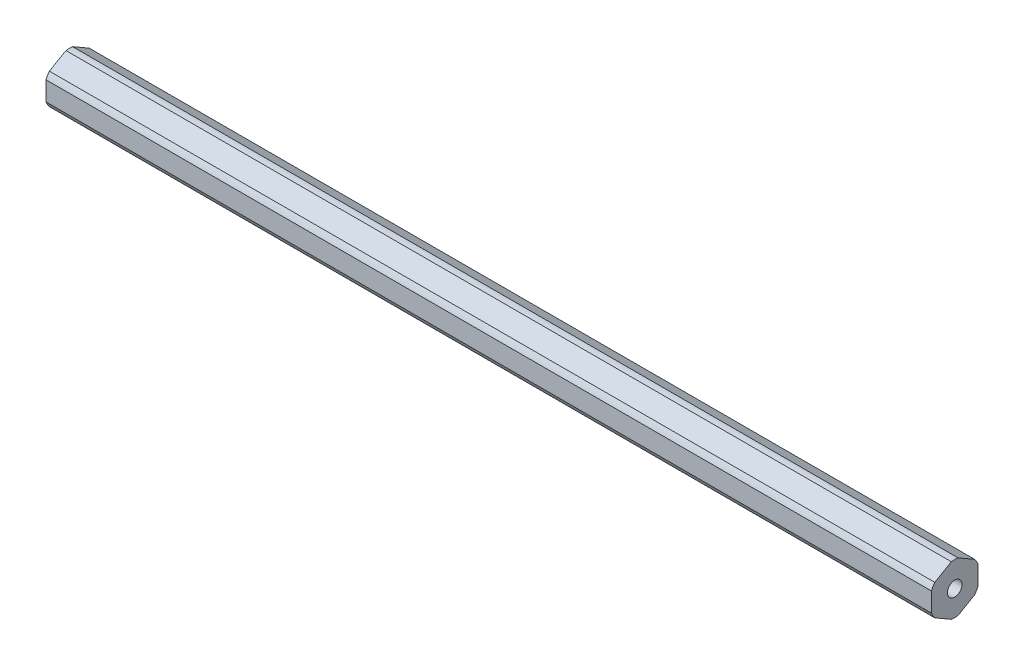
SolidWorks part; units mm, degrees
material "6061 Alloy"
ref_plane "Front Plane" through (0, 0, 0) normal (0, 0, 1) x (1, 0, 0)
ref_plane "Top Plane" through (0, 0, 0) normal (0, 1, 0) x (1, 0, 0)
ref_plane "Right Plane" through (0, 0, 0) normal (1, 0, 0) x (0, 0, -1)
ref_plane "Plane1" through (914.4, 0, 0) normal (1, 0, 0) x (0, 0, -1)
sketch "Sketch1" plane through (914.4, 0, 0) normal (1, 0, 0) x (0, 0, -1)
  line L0 (-5.4343, -4.1949) -> (-0.9157, -6.8037)
  line L1 (0.9157, -6.8037) -> (5.4343, -4.1949)
  line L2 (6.35, -2.6088) -> (6.35, 2.6088)
  line L3 (5.4343, 4.1949) -> (0.9157, 6.8037)
  line L4 (-0.9157, 6.8037) -> (-5.4343, 4.1949)
  line L5 (-6.35, 2.6088) -> (-6.35, -2.6088)
  circle A0 centre (0, 0) radius 1.9939
  arc A1 (-6.35, -2.6088) -> (-5.4343, -4.1949) centre (0, 0) ccw
  arc A2 (-0.9157, -6.8037) -> (0.9157, -6.8037) centre (0, 0) ccw
  arc A3 (5.4343, -4.1949) -> (6.35, -2.6088) centre (0, 0) ccw
  arc A4 (6.35, 2.6088) -> (5.4343, 4.1949) centre (0, 0) ccw
  arc A5 (0.9157, 6.8037) -> (-0.9157, 6.8037) centre (0, 0) ccw
  arc A6 (-5.4343, 4.1949) -> (-6.35, 2.6088) centre (0, 0) ccw
extrude "Boss-Extrude1" add sketch "Sketch1" against normal mid plane 241.427
equation "\"Hex Length\"= 7.125 + 2.38"
equation "\"D1@Boss-Extrude1\"=\"Hex Length\""
